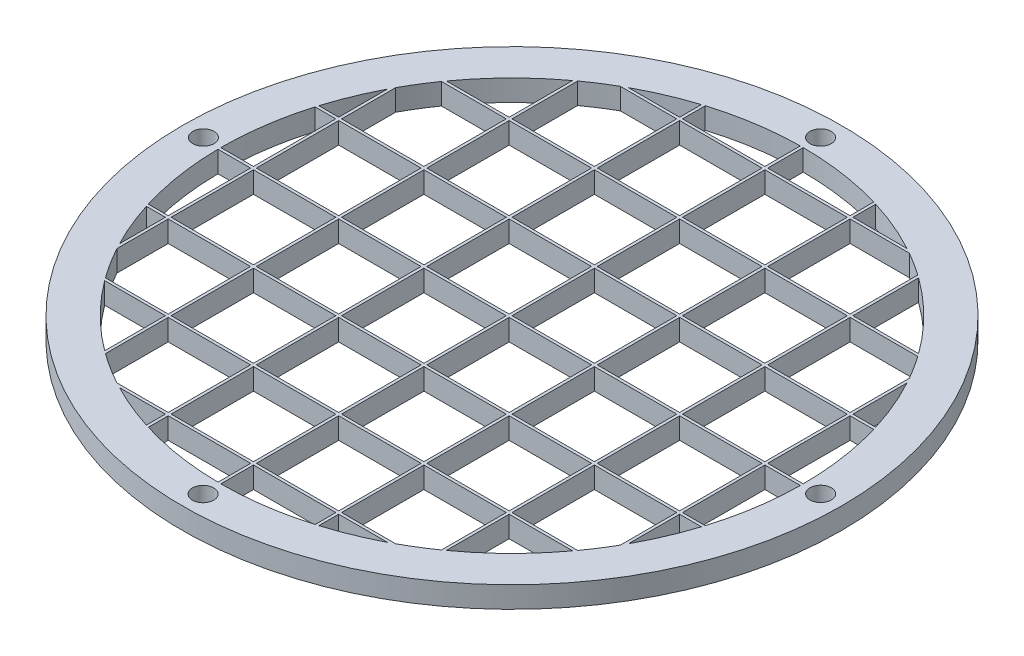
SolidWorks part; units mm, degrees
ref_plane "Front Plane" through (0, 0, 0) normal (0, 0, 1) x (1, 0, 0)
ref_plane "Top Plane" through (0, 0, 0) normal (0, 1, 0) x (1, 0, 0)
ref_plane "Right Plane" through (0, 0, 0) normal (1, 0, 0) x (0, 0, -1)
sketch "Sketch2" plane through (0, 0, 0) normal (0, 1, 0) x (1, 0, 0)
  circle A1 centre (0, 0) radius 41
  circle A2 centre (0, 0) radius 46
  point P208 (0, 0)
extrude "Boss-Extrude2" add sketch "Sketch2" along normal blind 3
sketch "Sketch4" plane through (0, 3, 0) normal (0, 1, 0) x (1, 0, 0)
  line L0 (0, 46) -> (0, -46)
  line L1 (12, 44.4072) -> (12, -44.4072)
  line L2 (24, 39.2428) -> (24, -39.2428)
  line L3 (36, 28.6356) -> (36, -28.6356)
  line L4 (-12, 44.4072) -> (-12, -44.4072)
  line L5 (-24, 39.2428) -> (-24, -39.2428)
  line L6 (-36, 28.6356) -> (-36, -28.6356)
  line L7 (-46, 0) -> (46, 0)
  line L8 (-44.4072, -12) -> (44.4072, -12)
  line L9 (-39.2428, -24) -> (39.2428, -24)
  line L10 (-28.6356, -36) -> (28.6356, -36)
  line L11 (-44.4072, 12) -> (44.4072, 12)
  line L12 (-39.2428, 24) -> (39.2428, 24)
  line L13 (-28.6356, 36) -> (28.6356, 36)
  circle A1 centre (0, 0) radius 46 construction
  circle A2 centre (0, 0) radius 46
  dimension "D1" = 4
  dimension "D2" = 4
extrude "Extrude-Thin5" add sketch "Sketch4" against normal blind 3 thin thin type one direction wall 0.4
sketch "Sketch5" plane through (0, 0, 0) normal (0, -1, 0) x (1, 0, 0)
  circle A0 centre (0, -43.4524) radius 1.5
  circle A1 centre (-43.4524, 0) radius 1.5
  circle A3 centre (43.4524, 0) radius 1.5
  circle A4 centre (0, 43.4524) radius 1.5 [skipped]
  point P11 (0, 0)
  dimension "D1" = 4
extrude "Cut-Extrude1" cut sketch "Sketch5" against normal blind 3
sketch "Sketch6" plane through (0, 3, 0) normal (0, 1, 0) x (1, 0, 0)
  circle A1 centre (0, -43.5) radius 1.5
  point P36 (0, 3)
  dimension "D1" = 43.5
extrude "Cut-Extrude2" cut sketch "Sketch6" against normal through all
